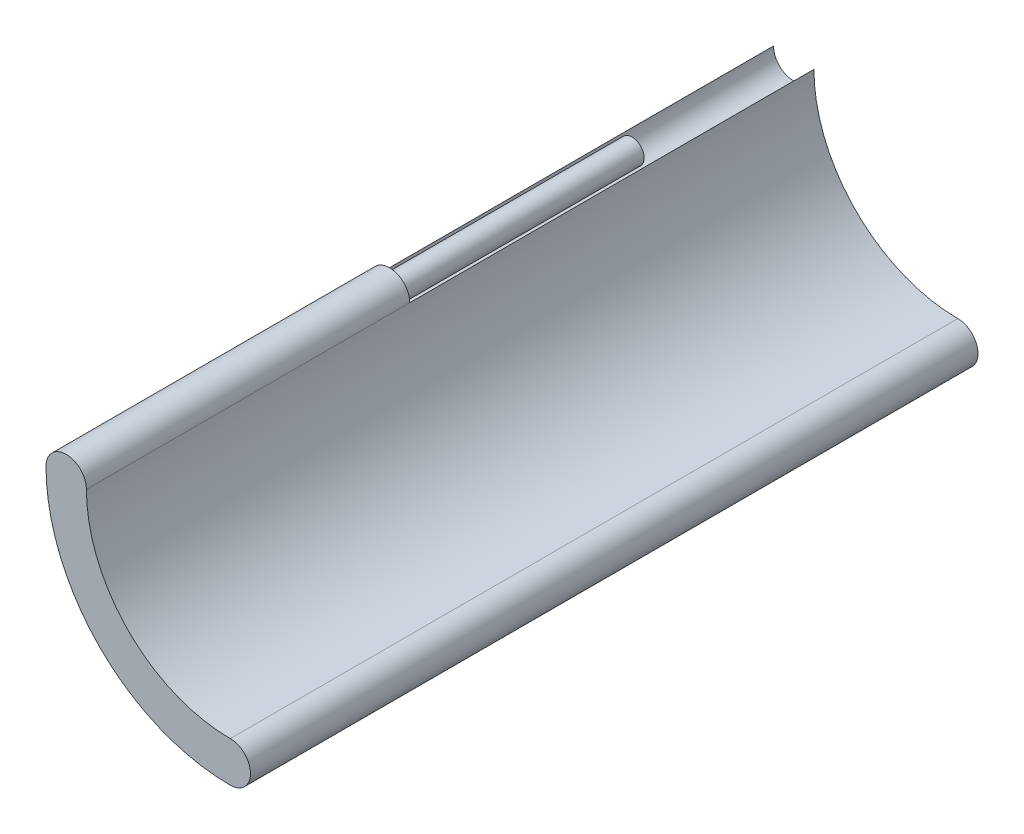
SolidWorks part; units mm, degrees
material "Commercialement pur CP-Ti UNS R50400 (SS)"
ref_plane "Plan de face" through (0, 0, 0) normal (0, 0, 1) x (1, 0, 0)
ref_plane "Plan de dessus" through (0, 0, 0) normal (0, 1, 0) x (1, 0, 0)
ref_plane "Plan de droite" through (0, 0, 0) normal (1, 0, 0) x (0, 0, -1)
sketch "Esquisse1" plane through (0, 0, 0) normal (0, 0, 1) x (1, 0, 0)
  line L0 (-114, 0) -> (114, 0) construction
  line L1 (0, -89) -> (0, -114) construction
  line L2 (-89, 0) -> (-114, 0) construction
  circle A0 centre (0, 0) radius 89
  circle A1 centre (0, 0) radius 114
  circle A2 centre (0, -101.5) radius 12.5
  circle A3 centre (-101.5, 0) radius 12.5
  circle A4 centre (-101.5, 0) radius 7.5
  dimension "D1" = 178
  dimension "D2" = 228
  dimension "D3" = 15
extrude "Boss.-Extru.1" add sketch "Esquisse1" against normal blind 450 contours A3 A1 A2 A0 | A2 region at (-66.5645, -66.5645, 0) region at (0, -101.5, 0)
extrude "Boss.-Extru.2" add sketch "Esquisse1<3>" against normal blind 350 separate body contours A4 region at (-101.5, 0, 0)
sketch "Esquisse1<3>" plane through (0, 0, 0) normal (0, 0, 1) x (1, 0, 0) same geometry as "Esquisse1"
extrude "Boss.-Extru.3" add sketch "Esquisse1<4>" against normal blind 200 contours A3 A4 region at (-101.5, -12.1464, 0)
sketch "Esquisse1<4>" plane through (0, 0, 0) normal (0, 0, 1) x (1, 0, 0) same geometry as "Esquisse1"
